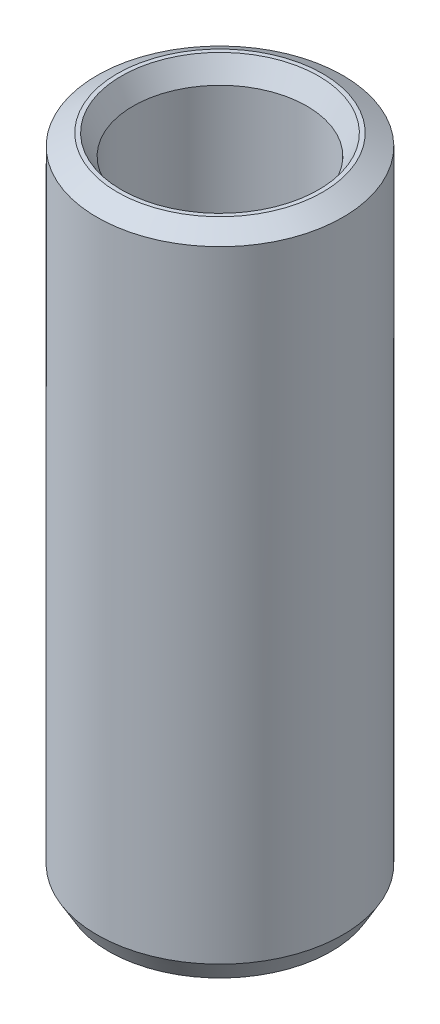
SolidWorks part; units mm, degrees
ref_plane "Front Plane" through (0, 0, 0) normal (0, 0, 1) x (1, 0, 0)
ref_plane "Top Plane" through (0, 0, 0) normal (0, 1, 0) x (1, 0, 0)
ref_plane "Right Plane" through (0, 0, 0) normal (1, 0, 0) x (0, 0, -1)
sketch "Sketch1" plane through (0, 0, 0) normal (0, 1, 0) x (1, 0, 0)
  circle A0 centre (0, 0) radius 30
  dimension "SLEEVE_OD" = 60
extrude "Boss-Extrude1" add sketch "Sketch1" along normal blind 159.4328
sketch "Sketch2" plane through (0, 0, 0) normal (0, 1, 0) x (1, 0, 0)
  circle A0 centre (0, 0) radius 21.2144
  dimension "BORE_D" = 42.4288
extrude "Cut-Extrude1" cut sketch "Sketch2" along normal through all
chamfer "Chamfer1" distance 2.8487 angle 60 4 edges at (0, 159.4328, 21.2144) (0, 0, 21.2144) (0, 0, 30) (0, 159.4328, 30) first distance on face at (0, 159.4328, 21.2144) first distance on face at (0, 0, 21.2144) first distance on face at (0, 159.4328, 30)
